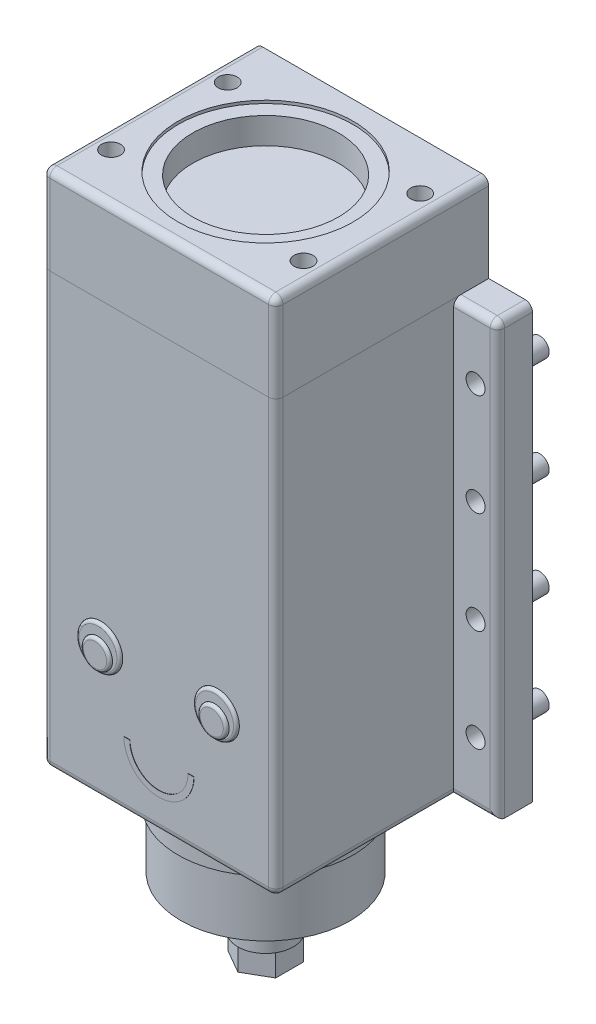
SolidWorks part; units mm, degrees
ref_plane "Front Plane" through (0, 0, 0) normal (0, 0, 1) x (1, 0, 0)
ref_plane "Top Plane" through (0, 0, 0) normal (0, 1, 0) x (1, 0, 0)
ref_plane "Right Plane" through (0, 0, 0) normal (1, 0, 0) x (0, 0, -1)
sketch "Sketch1" plane through (0, 0, 0) normal (0, 0, 1) x (1, 0, 0)
  line L0 (0, 74) -> (0, -74) construction
  line L1 (-55, -74) -> (55, -74)
  line L2 (-55, -74) -> (-55, 74)
  line L3 (-55, 74) -> (55, 74)
  line L4 (55, -74) -> (55, 74)
  line L5 (-55, -74) -> (55, 74) construction
  line L6 (-55, 74) -> (55, -74) construction
  circle A0 centre (47.5, -52.5) radius 3.25
  circle A1 centre (47.5, -17.5) radius 3.25
  circle A2 centre (47.5, 17.5) radius 3.25
  circle A3 centre (47.5, 52.5) radius 3.25
  circle A4 centre (-47.5, -52.5) radius 3.25
  circle A5 centre (-47.5, -17.5) radius 3.25
  circle A6 centre (-47.5, 17.5) radius 3.25
  circle A7 centre (-47.5, 52.5) radius 3.25
  point P0 (0, 0)
  dimension "D5" = 6.5
  dimension "D1" = 110
  dimension "D2" = 148
  dimension "D3" = 47.5
  dimension "D4" = 21.5
  dimension "D7" = 21.5
  dimension "D6" = 4
extrude "Boss-Extrude1" add sketch "Sketch1" along normal blind 12
sketch "Sketch3" plane through (0, 0, 0) normal (0, 0, -1) x (-1, 0, 0)
  circle A0 centre (-47.5, 52.5) radius 3.25
  circle A1 centre (-47.5, 17.5) radius 3.25
  circle A2 centre (-47.5, -17.5) radius 3.25
  circle A3 centre (-47.5, -52.5) radius 3.25
  circle A4 centre (47.5, -52.5) radius 3.25
  circle A5 centre (47.5, -17.5) radius 3.25
  circle A6 centre (47.5, 17.5) radius 3.25
  circle A7 centre (47.5, 52.5) radius 3.25
  dimension "D1" = 6.5
  dimension "D2" = 6.5
  dimension "D3" = 6.5
  dimension "D4" = 6.5
  dimension "D5" = 6.5
  dimension "D6" = 6.5
  dimension "D7" = 6.5
  dimension "D8" = 6.5
extrude "Boss-Extrude2" add sketch "Sketch3" along normal blind 10 separate body
sketch "Sketch4" plane through (0, 0, 12) normal (0, 0, 1) x (1, 0, 0)
  line L0 (55, 74) -> (-55, 74) construction
  line L1 (-40, -74) -> (40, -74)
  line L2 (-40, -74) -> (-40, 74)
  line L3 (-40, 74) -> (40, 74)
  line L4 (40, -74) -> (40, 74)
  line L5 (-40, -74) -> (40, 74) construction
  line L6 (-40, 74) -> (40, -74) construction
  point P0 (0, 0)
  dimension "D1" = 80
extrude "Boss-Extrude3" add sketch "Sketch4" along normal blind 61
sketch "Sketch5" plane through (0, 74, 0) normal (0, 1, 0) x (1, 0, 0)
  line L0 (55, 0) -> (-55, 0) construction
  line L1 (-40, -73) -> (40, -73)
  line L2 (-40, -73) -> (-40, 0)
  line L3 (-40, 0) -> (40, 0)
  line L4 (40, -73) -> (40, 0)
extrude "Boss-Extrude4" add sketch "Sketch5" along normal blind 30 separate body
sketch "Sketch6" plane through (0, 104, 0) normal (0, 1, 0) x (1, 0, 0)
  line L0 (0, 0) -> (0, -73) construction
  line L1 (-40, -73) -> (40, -73) construction
  circle A0 centre (0, -36.5) radius 30
  circle A1 centre (0, -36.5) radius 25
  dimension "D1" = 60
  dimension "D2" = 50
extrude "Cut-Extrude1" cut sketch "Sketch6" against normal blind 1
sketch "Sketch8" plane through (0, 104, 0) normal (0, 1, 0) x (1, 0, 0)
  circle A0 centre (0, -36.5) radius 25
extrude "Cut-Extrude2" cut sketch "Sketch8" against normal blind 10
sketch "Sketch10" plane through (0, 104, 0) normal (0, 1, 0) x (1, 0, 0)
  line L0 (0, 0) -> (0, -73) construction
  line L1 (-40, -73) -> (40, -73) construction
  line L2 (-40, -36.5) -> (40, -36.5) construction
  line L3 (-40, 0) -> (-40, -73) construction
  line L4 (40, -73) -> (40, 0) construction
  circle A0 centre (33, -16.5) radius 3.25
  circle A1 centre (33, -56.5) radius 3.25
  circle A2 centre (-33, -56.5) radius 3.25
  circle A3 centre (-33, -16.5) radius 3.25
  dimension "D3" = 6.5
  dimension "D1" = 33
  dimension "D2" = 20
extrude "Cut-Extrude3" cut sketch "Sketch10" against normal blind 10
sketch "Sketch11" plane through (0, -74, 0) normal (0, -1, 0) x (1, 0, 0)
  line L0 (0, 0) -> (0, 73) construction
  line L1 (40, 73) -> (-40, 73)
  line L2 (40, 73) -> (40, 0)
  line L3 (40, 0) -> (-40, 0)
  line L4 (-40, 73) -> (-40, 0)
  circle A0 centre (0, 36.5) radius 30
  dimension "D1" = 60
extrude "Boss-Extrude5" add sketch "Sketch11" along normal blind 10 contours A0
sketch "Sketch13" plane through (0, -84, 0) normal (0, -1, 0) x (1, 0, 0)
  line L0 (0, 6.5) -> (0, 66.5) construction
  circle A0 centre (0, 36.5) radius 30 construction
  circle A1 centre (0, 36.5) radius 30 construction
  circle A2 centre (0, 36.5) radius 29
  dimension "D1" = 58
extrude "Boss-Extrude6" add sketch "Sketch13" along normal blind 20
sketch "Sketch14" plane through (0, -104, 0) normal (0, -1, 0) x (1, 0, 0)
  circle A0 centre (0, 36.5) radius 7.5
  dimension "D1" = 15
extrude "Boss-Extrude7" add sketch "Sketch14" along normal blind 10
sketch "Sketch15" plane through (0, -114, 0) normal (0, -1, 0) x (1, 0, 0)
  circle A0 centre (0, 36.5) radius 9.5
  dimension "D1" = 19
extrude "Boss-Extrude8" add sketch "Sketch15" along normal blind 7.5
sketch "Sketch16" plane through (0, -121.5, 0) normal (0, -1, 0) x (1, 0, 0)
  line L0 (-40, 73) -> (40, 73) construction
  line L1 (-8.2272, 41.25) -> (-8.2272, 31.75)
  line L2 (-8.2272, 31.75) -> (0, 27)
  line L3 (0, 27) -> (8.2272, 31.75)
  line L4 (8.2272, 31.75) -> (8.2272, 41.25)
  line L5 (8.2272, 41.25) -> (0, 46)
  line L6 (0, 46) -> (-8.2272, 41.25)
  line L7 (40, 73) -> (40, 0) construction
  line L8 (40, 36.5) -> (-40, 36.5) construction
  line L9 (-40, 73) -> (-40, 12) construction
  circle A0 centre (0, 36.5) radius 8.2272 construction
  circle A1 centre (0, 36.5) radius 9.5 construction
extrude "Boss-Extrude9" add sketch "Sketch16" along normal blind 7.5
sketch "Sketch17" plane through (0, -129, 0) normal (0, -1, 0) x (1, 0, 0)
  circle A0 centre (0, 36.5) radius 5.75
  dimension "D1" = 11.5
extrude "Cut-Extrude4" cut sketch "Sketch17" against normal blind 18
sketch "Sketch18" plane through (0, -104, 0) normal (0, -1, 0) x (1, 0, 0)
  line L0 (-29, 36.5) -> (29, 36.5) construction
  line L1 (0, 65.5) -> (0, 7.5) construction
  circle A0 centre (0, 36.5) radius 29
  circle A1 centre (15, 51.5) radius 3.25
  circle A2 centre (15, 21.5) radius 3.25
  circle A3 centre (-15, 21.5) radius 3.25
  circle A4 centre (-15, 51.5) radius 3.25
  dimension "D1" = 58
  dimension "D2" = 6.5
  dimension "D3" = 15
  dimension "D4" = 15
extrude "Cut-Extrude6" cut sketch "Sketch18" against normal blind 5 contours A2 | A3 | A1 | A4
fillet "Fillet1" radius 2.5 13 edges at (55, 74, 6) (47.5, 74, 12) (-47.5, 74, 12) (-55, 74, 6) (-40, -74, 42.5) (40, -74, 42.5) (47.5, -74, 12) (-47.5, -74, 12) (-55, 0, 12) (0, -74, 73) (-40, 0, 73) (55, 0, 12) (40, 0, 73)
fillet "Fillet2" radius 2.5 5 edges at (-40, 89, 73) (40, 89, 73) (40, 104, 36.5) (0, 104, 73) (-40, 104, 36.5)
sketch "Sketch19" plane through (0, 0, 73) normal (0, 0, 1) x (1, 0, 0)
  line L0 (0, 74) -> (0, -71.5) construction
  line L1 (37.5, 74) -> (-37.5, 74) construction
  line L2 (-37.5, -71.5) -> (37.5, -71.5) construction
  line L3 (-37.5, 1.25) -> (37.5, 1.25) construction
  line L4 (-37.5, 74) -> (-37.5, -71.5) construction
  line L5 (37.5, -71.5) -> (37.5, 74) construction
  circle A0 centre (-20, -28.75) radius 7.5
  circle A1 centre (20, -28.75) radius 7.5
  dimension "D3" = 15
  dimension "D1" = 30
  dimension "D2" = 20
extrude "Boss-Extrude10" add sketch "Sketch19" along normal blind 1
sketch "Sketch20" plane through (0, 0, 74) normal (0, 0, 1) x (1, 0, 0)
  line L0 (0, 0) -> (0, -71.5) construction
  line L2 (-20, -21.25) -> (-20, -36.25) construction
  line L3 (-27.5, -28.75) -> (-12.5, -28.75) construction
  line L4 (-37.5, -71.5) -> (37.5, -71.5) construction
  circle A0 centre (-20, -28.75) radius 7.5 construction
  circle A1 centre (-20, -28.75) radius 7.5 construction
  circle A2 centre (-20, -30.25) radius 5
  circle A3 centre (20, -30.25) radius 5
  dimension "D1" = 10
  dimension "D2" = 6
extrude "Boss-Extrude11" add sketch "Sketch20" along normal blind 1
fillet "Fillet4" radius 1 2 edges at (12.5, -28.75, 74) (-12.5, -28.75, 74)
fillet "Fillet5" radius 1 2 edges at (15, -30.25, 75) (-15, -30.25, 75)
sketch "Sketch21" plane through (0, 0, 73) normal (0, 0, 1) x (1, 0, 0)
  line L0 (0, 0) -> (0, -71.5) construction
  line L1 (-37.5, -71.5) -> (37.5, -71.5) construction
  line L2 (-12, -51.5) -> (-10, -51.5)
  line L3 (12, -51.5) -> (10, -51.5)
  arc A0 (-10, -51.5) -> (10, -51.5) centre (0, -51.5) ccw
  arc A1 (-12, -51.5) -> (12, -51.5) centre (0, -51.5) ccw
  dimension "D1" = 2
  dimension "D2" = 20
  dimension "D3" = 10
extrude "Boss-Extrude12" add sketch "Sketch21" along normal blind 0.1
